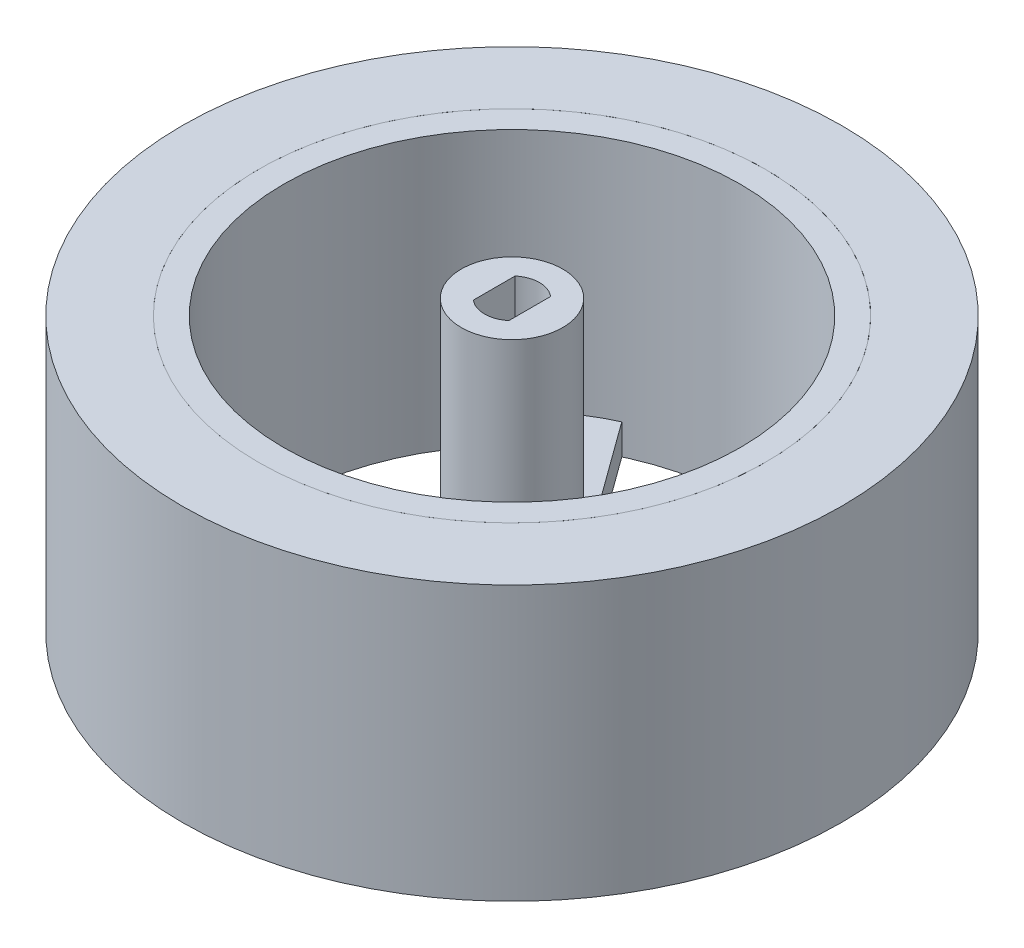
SolidWorks part; units mm, degrees
ref_plane "Front Plane" through (0, 0, 0) normal (0, 0, 1) x (1, 0, 0)
ref_plane "Top Plane" through (0, 0, 0) normal (0, 1, 0) x (1, 0, 0)
ref_plane "Right Plane" through (0, 0, 0) normal (1, 0, 0) x (0, 0, -1)
sketch "Sketch1" plane through (0, 0, 0) normal (0, 1, 0) x (1, 0, 0)
  circle A0 centre (0, 0) radius 32.5
  circle A1 centre (0, 0) radius 25
  dimension "D1" = 65
  dimension "D2" = 50
extrude "Boss-Extrude1" add sketch "Sketch1" along normal blind 27
sketch "Sketch2" plane through (0, 0, 0) normal (0, -1, 0) x (1, 0, 0)
  circle A0 centre (0, 0) radius 25
  circle A1 centre (0, 0) radius 22.5
  circle A2 centre (0, 0) radius 25 construction
  dimension "D1" = 45
extrude "Boss-Extrude2" add sketch "Sketch2" against normal up to surface (27 mm away) separate body up to face at (0, 27, 32.5)
sketch "Sketch3" plane through (0, 0, 0) normal (0, -1, 0) x (1, 0, 0)
  line L0 (0, 0) -> (0, 22.5) construction
  line L1 (4.25, 8.0368) -> (6.3301, 6.5255)
  line L2 (4.25, 22.095) -> (4.25, 8.0368)
  line L3 (19.7002, 10.8697) -> (6.3301, 6.5255)
  line L5 (1, 22.4778) -> (1, 9)
  line L7 (0, 0) -> (13.2252, 18.2029) construction
  line L8 (21.0686, 7.8971) -> (8.2505, 3.7322)
  line L9 (1, 9) -> (0, 9) construction
  line L10 (0, 0) -> (21.3988, 6.9529) construction
  line L11 (8.2505, 3.7322) -> (8.5595, 2.7812) construction
  line L12 (8.8685, 1.8301) -> (8.5595, 2.7812) construction
  line L13 (21.6866, 5.995) -> (8.8685, 1.8301)
  line L14 (22.3269, 2.7857) -> (8.9568, -1.5585)
  line L15 (8.9568, -1.5585) -> (8.1622, -4.0038)
  line L16 (16.4254, -15.3771) -> (8.1622, -4.0038)
  line L17 (14.0211, -17.5971) -> (6.0991, -6.6934)
  line L18 (4.4811, -7.8689) -> (5.2901, -7.2812) construction
  line L19 (12.4031, -18.7727) -> (4.4811, -7.8689)
  line L20 (9.5488, -20.3733) -> (1.2856, -9)
  line L21 (1.2856, -9) -> (-1.2856, -9)
  line L22 (-9.5488, -20.3733) -> (-1.2856, -9)
  line L23 (-12.4031, -18.7727) -> (-4.4811, -7.8689)
  line L24 (-6.0991, -6.6934) -> (-5.2901, -7.2812) construction
  line L25 (-14.0211, -17.5971) -> (-6.0991, -6.6934)
  line L26 (-16.4254, -15.3771) -> (-8.1622, -4.0038)
  line L27 (-8.1622, -4.0038) -> (-8.9568, -1.5585)
  line L28 (-22.3269, 2.7857) -> (-8.9568, -1.5585)
  line L29 (-21.6866, 5.995) -> (-8.8685, 1.8301)
  line L30 (-8.2505, 3.7322) -> (-8.5595, 2.7812) construction
  line L31 (-21.0686, 7.8971) -> (-8.2505, 3.7322)
  line L32 (-19.7002, 10.8697) -> (-6.3301, 6.5255)
  line L33 (-6.3301, 6.5255) -> (-4.25, 8.0368)
  line L34 (-4.25, 22.095) -> (-4.25, 8.0368)
  line L35 (-1, 22.4778) -> (-1, 9)
  line L36 (-1, 9) -> (1, 9)
  line L37 (-8.8685, 1.8301) -> (-8.2505, 3.7322)
  line L38 (-4.4811, -7.8689) -> (-6.0991, -6.6934)
  line L39 (4.4811, -7.8689) -> (6.0991, -6.6934)
  line L40 (8.2505, 3.7322) -> (8.8685, 1.8301)
  circle A0 centre (0, 0) radius 22.5 construction
  arc A1 (1, 22.4778) -> (4.25, 22.095) centre (0, 0) cw
  arc A2 (21.0686, 7.8971) -> (19.7002, 10.8697) centre (0, 0) ccw
  arc A3 (21.6866, 5.995) -> (22.3269, 2.7857) centre (0, 0) cw
  arc A4 (14.0211, -17.5971) -> (16.4254, -15.3771) centre (0, 0) ccw
  arc A5 (12.4031, -18.7727) -> (9.5488, -20.3733) centre (0, 0) cw
  arc A6 (-12.4031, -18.7727) -> (-9.5488, -20.3733) centre (0, 0) ccw
  arc A7 (-14.0211, -17.5971) -> (-16.4254, -15.3771) centre (0, 0) cw
  arc A8 (-21.6866, 5.995) -> (-22.3269, 2.7857) centre (0, 0) ccw
  arc A9 (-21.0686, 7.8971) -> (-19.7002, 10.8697) centre (0, 0) cw
  arc A10 (-1, 22.4778) -> (-4.25, 22.095) centre (0, 0) ccw
  point P13 (5.2901, 7.2812)
  point P57 (0, 0)
  dimension "D1" = 9
  dimension "D2" = 9
  dimension "D3" = 3.25
  dimension "D4" = 1
  dimension "D5" = 36
  dimension "D6" = 72
  dimension "D7" = 5
extrude "Boss-Extrude3" add sketch "Sketch3" against normal blind 3 separate body
sketch "Sketch4" plane through (0, 0, 0) normal (0, -1, 0) x (1, 0, 0)
  circle A0 centre (0, 0) radius 0.75
  dimension "D1" = 1.5
extrude "Cut-Extrude1" cut sketch "Sketch4" against normal up to surface (3 mm away) up to face at (0, 3, 0)
sketch "Sketch5" plane through (0, 3, 0) normal (0, 1, 0) x (1, 0, 0)
  line L0 (1.75, 2.0561) -> (1.75, -2.0561)
  line L1 (0, 0) -> (0, 2.7) construction
  line L2 (0, 0) -> (1.75, 0) construction
  line L3 (-1.75, 2.0561) -> (-1.75, -2.0561)
  circle A0 centre (0, 0) radius 5
  arc A1 (-1.75, 2.0561) -> (1.75, 2.0561) centre (0, 0) cw
  arc A2 (-1.75, -2.0561) -> (1.75, -2.0561) centre (0, 0) ccw
  point P10 (-1.75, 0)
  dimension "D3" = 10
  dimension "D1" = 2.7
  dimension "D2" = 1.75
extrude "Boss-Extrude4" add sketch "Sketch5" along normal blind 25.5 separate body
